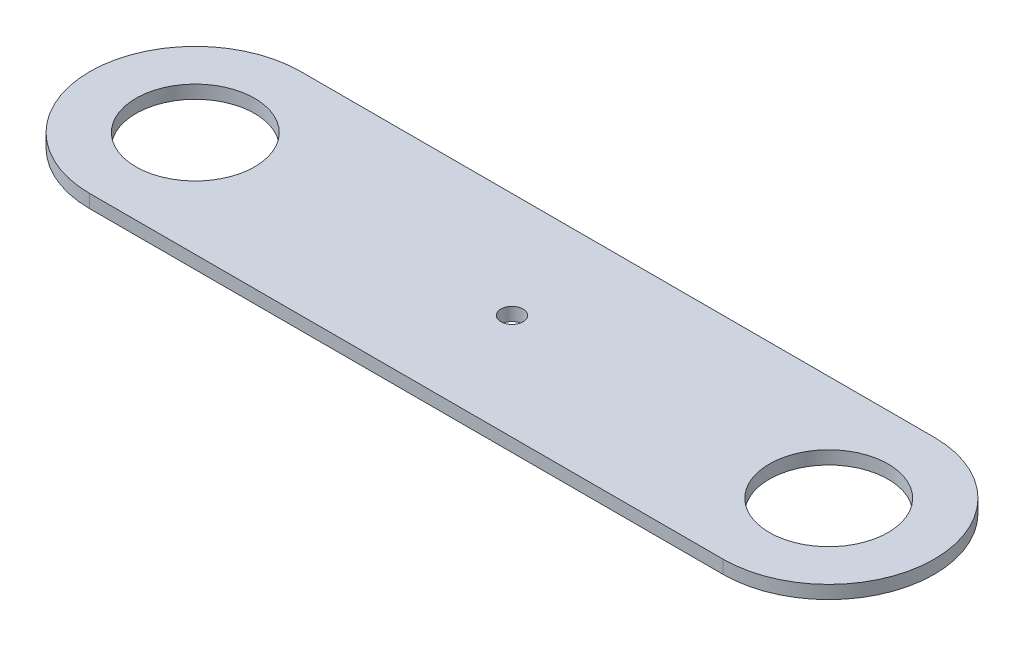
SolidWorks part; units mm, degrees
ref_plane "Front" through (0, 0, 0) normal (0, 0, 1) x (1, 0, 0)
ref_plane "Top" through (0, 0, 0) normal (0, 1, 0) x (1, 0, 0)
ref_plane "Right" through (0, 0, 0) normal (1, 0, 0) x (0, 0, -1)
sketch "Sketch1" plane through (0, 0, 0) normal (0, 1, 0) x (1, 0, 0)
  line L0 (0, 0) -> (152.4, 0) construction
  line L1 (0, 0) -> (152.4, 0) construction
  line L2 (0, 25.4) -> (152.4, 25.4)
  line L3 (0, -25.4) -> (152.4, -25.4)
  circle A0 centre (0, 0) radius 14.2875
  circle A1 centre (152.4, 0) radius 14.2875
  arc A2 (0, 25.4) -> (0, -25.4) centre (0, 0) ccw
  arc A3 (152.4, -25.4) -> (152.4, 25.4) centre (152.4, 0) ccw
  point P5 (76.2, 0)
  point P10 (76.2, -25.4)
  dimension "D1" = 28.575
  dimension "D2" = 28.575
  dimension "D3" = 152.4
  dimension "D4" = 50.8
extrude "Boss-Extrude1" add sketch "Sketch1" along normal blind 3.175
sketch "Sketch2" plane through (0, 3.175, 0) normal (0, 1, 0) x (1, 0, 0)
  line L0 (0, 0) -> (152.4, 0) construction
  circle A0 centre (76.2, 0) radius 2.667
  dimension "D1" = 5.334
extrude "Cut-Extrude1" cut sketch "Sketch2" against normal up to next
